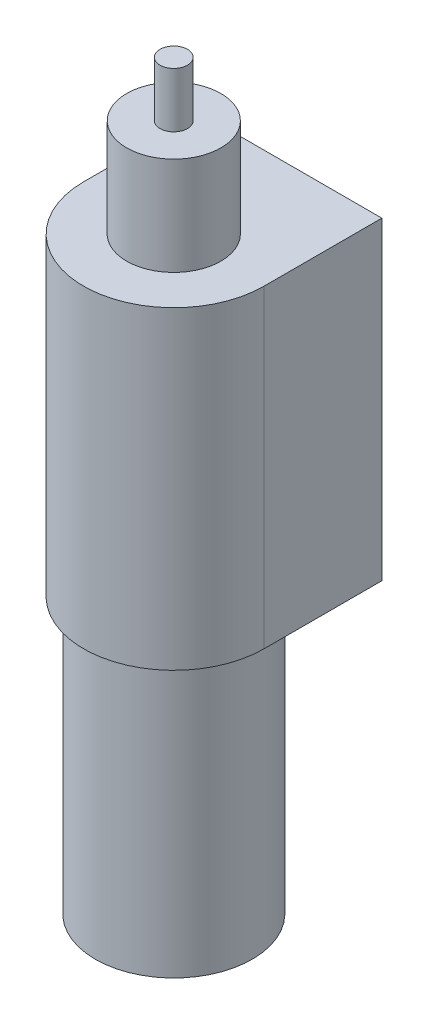
SolidWorks part; units mm, degrees
ref_plane "Plano frontal" through (0, 0, 0) normal (0, 0, 1) x (1, 0, 0)
ref_plane "Plano superior" through (0, 0, 0) normal (0, 1, 0) x (1, 0, 0)
ref_plane "Plano direito" through (0, 0, 0) normal (1, 0, 0) x (0, 0, -1)
sketch "Esboço2" plane through (0, 0, 0) normal (0, 1, 0) x (1, 0, 0)
  circle A0 centre (0, 0) radius 2
  dimension "D1" = 4
extrude "Ressalto-extrusão1" add sketch "Esboço2" along normal blind 15
sketch "Esboço3" plane through (0, 15, 0) normal (0, 1, 0) x (1, 0, 0)
  circle A0 centre (0, 0) radius 1.2
  dimension "D1" = 2.4
extrude "Ressalto-extrusão2" add sketch "Esboço3" along normal blind 2.5
sketch "Esboço4" plane through (0, 17.5, 0) normal (0, 1, 0) x (1, 0, 0)
  circle A0 centre (0, 0) radius 0.35
  dimension "D1" = 0.7
extrude "Ressalto-extrusão3" add sketch "Esboço4" along normal blind 1.4
ref_axis "Eixo1" through (0, 19.1555, 0) along (0, -1, 0)
sketch "Esboço5" plane through (0, 15, 0) normal (0, 1, 0) x (1, 0, 0)
  circle A0 centre (0, 0) radius 2.3
  circle A1 centre (0, 0) radius 2
  circle A2 centre (0, 0) radius 2
  dimension "D1" = 0
  dimension "D2" = 0.3
extrude "Ressalto-extrusão4" add sketch "Esboço5" against normal blind 8
ref_plane "Plano1" through (0, 0, 0) normal (0, 0, 1) x (0, -1, 0)
sketch "Esboço6" plane through (0, 15, 0) normal (0, 1, 0) x (1, 0, 0)
  line L0 (3.33, 3) -> (4.53, 3) construction
  line L1 (-2.3, 0) -> (2.3, 0)
  line L2 (-2.3, 0) -> (-2.3, 3)
  line L3 (-2.3, 3) -> (2.3, 3)
  line L4 (2.3, 0) -> (2.3, 3)
  circle A1 centre (0, 0) radius 2.3 construction
  circle A2 centre (0, 0) radius 2.3
  circle M3 centre (0, 0) radius 2.3
extrude "Ressalto-extrusão6" add sketch "Esboço6" against normal up to surface (8 mm away) contours L4 L3 M3 | L3 L2 M3 region at (-2.2451, 15, -1.5) up to face at (0, 7, 2)
